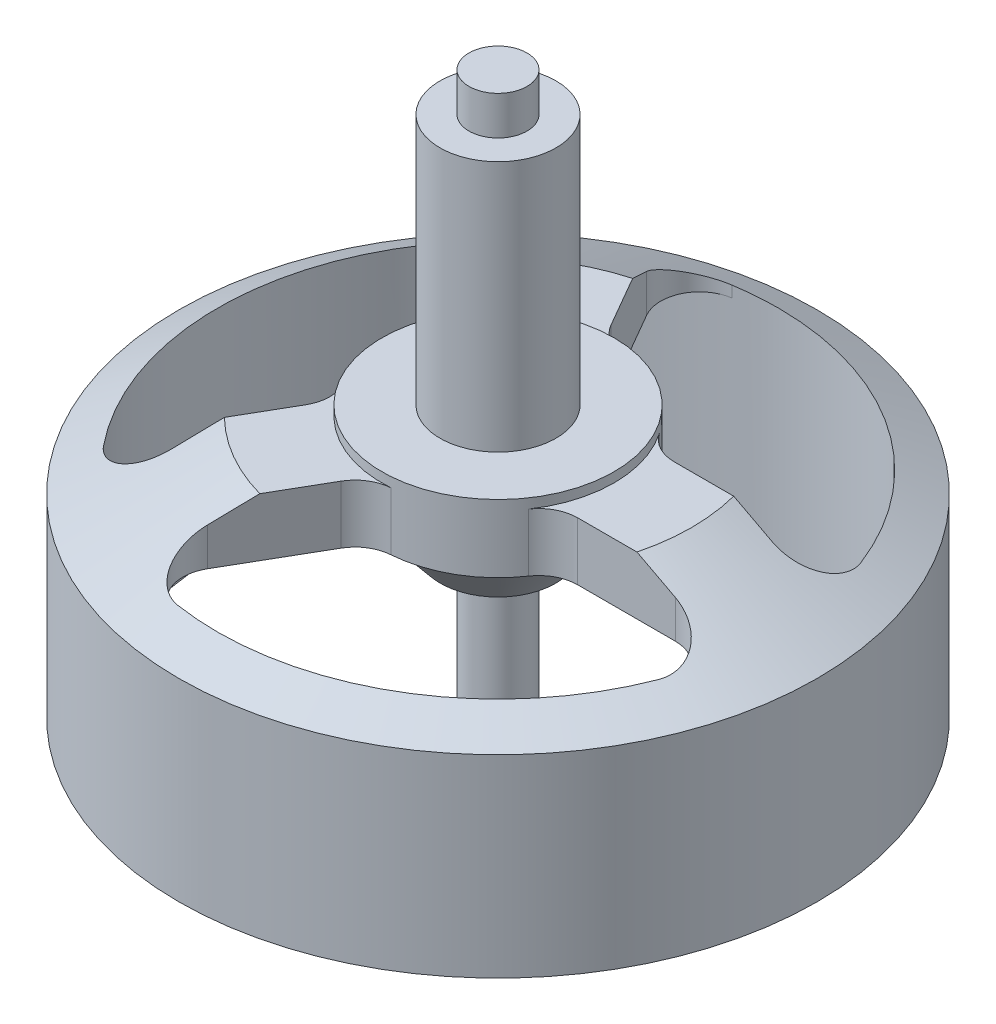
SolidWorks part; units mm, degrees
material "Custom Plastic"
ref_plane "Front Plane" through (0, 0, 0) normal (0, 0, 1) x (1, 0, 0)
ref_plane "Top Plane" through (0, 0, 0) normal (0, 1, 0) x (1, 0, 0)
ref_plane "Right Plane" through (0, 0, 0) normal (1, 0, 0) x (0, 0, -1)
sketch "Sketch1" plane through (0, 0, 0) normal (0, 0, 1) x (1, 0, 0)
  line L0 (0, 0) -> (0, 29) construction
  line L1 (0, 0) -> (16.5, 0)
  line L2 (16.5, 0) -> (16.5, 10)
  line L3 (16.5, 10) -> (10, 13.5)
  line L4 (10, 13.5) -> (6, 13.5)
  line L5 (6, 13.5) -> (6, 14)
  line L6 (6, 14) -> (3, 14)
  line L7 (3, 14) -> (3, 27)
  line L8 (3, 27) -> (1.5, 27)
  line L9 (1.5, 27) -> (1.5, 29)
  line L10 (1.5, 29) -> (0, 29)
  line L11 (0, 0) -> (0, 29)
  dimension "D1" = 33
  dimension "D2" = 10
  dimension "D3" = 13.5
  dimension "D4" = 20
  dimension "D5" = 12
  dimension "D6" = 0.5
  dimension "D7" = 6
  dimension "D8" = 13
  dimension "D9" = 3
  dimension "D10" = 2
revolve "Revolve1" add sketch "Sketch1" angle 360 about L0
sketch "Sketch2" plane through (0, 0, 0) normal (0, -1, 0) x (1, 0, 0)
  circle A0 centre (0, 0) radius 14.5
  dimension "D1" = 29
extrude "Cut-Extrude1" cut sketch "Sketch2" against normal blind 10.5
sketch "Sketch3" plane through (0, 10.5, 0) normal (0, -1, 0) x (1, 0, 0)
  line L0 (-0.5621, -5.9736) -> (-4.9764, -13.6193)
  line L1 (5.4544, 2.5) -> (14.2829, 2.5)
  line L2 (-4.8922, -3.4736) -> (-9.3065, -11.1193)
  line L3 (5.4544, -2.5) -> (14.2829, -2.5)
  line L4 (-4.8922, 3.4736) -> (-9.3065, 11.1193)
  line L5 (5.4544, 2.5) -> (14.2829, -2.5) construction
  line L6 (5.4544, -2.5) -> (14.2829, 2.5) construction
  line L7 (-0.5621, 5.9736) -> (-4.9764, 13.6193)
  circle A0 centre (0, 0) radius 14.5
  arc A1 (5.4544, 2.5) -> (5.4544, -2.5) centre (0, 0) ccw
  circle A2 centre (0, 0) radius 16.5 construction
  circle A3 centre (0, 0) radius 14.5 construction
  point P6 (9.8686, 0)
  point P23 (0, 0)
  circle M4 centre (0, 0) radius 14.5
  dimension "D1" = 2
  dimension "D2" = 12
  dimension "D3" = 5
  dimension "D4" = 8.8285
  dimension "D5" = 3
extrude "Cut-Extrude2" cut sketch "Sketch3" against normal up to surface (5.1538 mm away) contours A1 L1 L7 M4 | A1 L4 L2 M4 | A1 L0 L3 M4 region at (4.915, 10.5, -8.5131) region at (-9.8301, 10.5, 0) region at (4.915, 10.5, 8.5131) up to face at (0, 13.5, -10)
fillet "Fillet1" radius 2 6 edges at (-9.3065, 10.7885, -11.1193) (-4.9764, 10.7885, -13.6193) (-9.3065, 10.7885, 11.1193) (14.2829, 10.7885, -2.5)
fillet "Fillet2" radius 2 6 edges at (5.4544, 12, 2.5) (-0.5621, 12, 5.9736) (-4.8922, 12, 3.4736) (-4.8922, 12, -3.4736) (-0.5621, 12, -5.9736) (5.4544, 12, -2.5)
sketch "Sketch4" plane through (0, 10.5, 0) normal (0, -1, 0) x (1, 0, 0)
  circle A0 centre (0, 0) radius 5.5
  arc A1 (0.4424, -5.9837) -> (4.9608, -3.375) centre (0, 0) ccw construction
  dimension "D1" = 0.5
extrude "Boss-Extrude1" add sketch "Sketch4" along normal blind 3 draft 40
sketch "Sketch5" plane through (0, 7.5, 0) normal (0, -1, 0) x (1, 0, 0)
  circle A0 centre (0, 0) radius 1.5
  dimension "D1" = 3
extrude "Boss-Extrude2" add sketch "Sketch5" along normal blind 13
sketch "Sketch7" plane through (0, -5.5, 0) normal (0, -1, 0) x (1, 0, 0)
  circle A0 centre (0, 0) radius 2
  circle A1 centre (0, 0) radius 1.5 construction
  dimension "D1" = 0.5
extrude "Boss-Extrude3" add sketch "Sketch7" along normal blind 1
